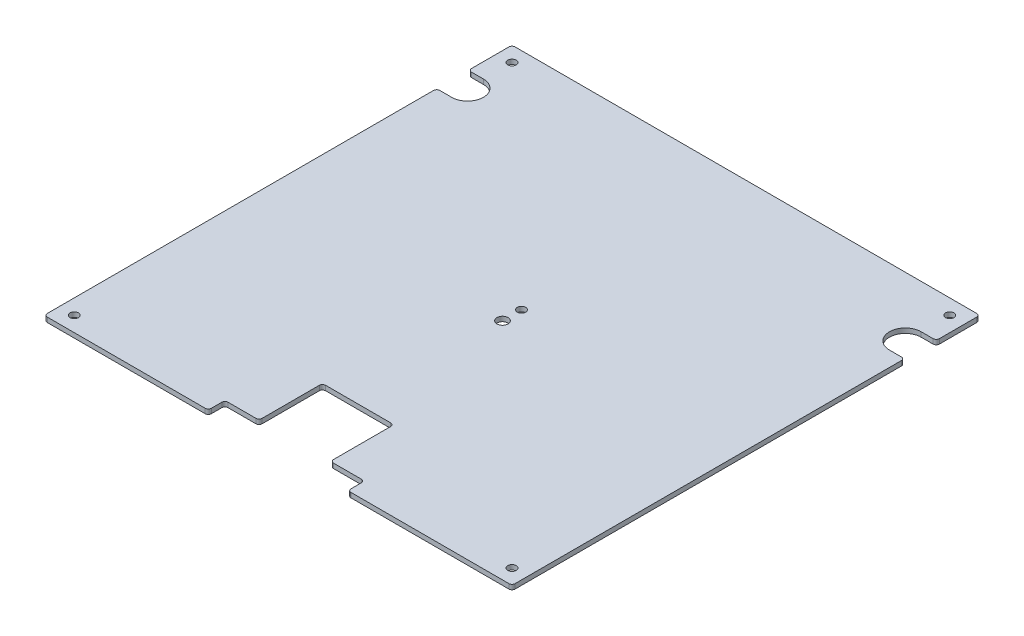
SolidWorks part; units mm, degrees
material "6061-T6 (SS)"
ref_plane "Front Plane" through (0, 0, 0) normal (0, 0, 1) x (1, 0, 0)
ref_plane "Top Plane" through (0, 0, 0) normal (0, 1, 0) x (1, 0, 0)
ref_plane "Right Plane" through (0, 0, 0) normal (1, 0, 0) x (0, 0, -1)
sketch "Sketch1" plane through (0, 0, 0) normal (0, 1, 0) x (1, 0, 0)
  line L1 (152, -152) -> (-152, -152)
  line L2 (152, -152) -> (152, 152)
  line L3 (152, 152) -> (-152, 152)
  line L4 (-152, -152) -> (-152, 152)
  line L5 (152, -152) -> (-152, 152) construction
  line L6 (152, 152) -> (-152, -152) construction
  point P0 (0, 0)
  dimension "D1" = 304
extrude "Boss-Extrude1" add sketch "Sketch1" along normal blind 3
sketch "Sketch2" plane through (0, 3, 0) normal (0, 1, 0) x (1, 0, 0)
  line L0 (-44, -152) -> (-44, -137)
  line L1 (-152, -152) -> (152, -152) construction
  line L2 (-44, -137) -> (44, -137)
  line L3 (44, -137) -> (44, -152)
  line L4 (44, -152) -> (-44, -152)
  line L5 (-152, 100) -> (-138, 100)
  line L6 (-152, 152) -> (-152, -152) construction
  line L8 (-138, 120) -> (-152, 120)
  line L9 (-152, 120) -> (-152, 100)
  line L10 (-152, 110) -> (-138, 110) construction
  line L11 (0, -152) -> (0, 152) construction
  line L12 (152, 152) -> (-152, 152) construction
  line L13 (152, 100) -> (138, 100)
  line L14 (152, 120) -> (152, 100)
  line L15 (138, 120) -> (152, 120)
  arc A0 (-138, 100) -> (-138, 120) centre (-138, 110) ccw
  arc A1 (138, 100) -> (138, 120) centre (138, 110) cw
  point P20 (0, 0)
  dimension "D1" = 108
  dimension "D2" = 196
  dimension "D3" = 15
  dimension "D4" = 20
  dimension "D5" = 262
  dimension "D6" = 14
extrude "Cut-Extrude1" cut sketch "Sketch2" against normal through all
sketch "Sketch7" plane through (0, 0, 0) normal (0, -1, 0) x (1, 0, 0)
  line L0 (44, 137) -> (-44, 137) construction
  line L1 (22.5, 97) -> (-22.5, 97)
  line L2 (22.5, 97) -> (22.5, 137)
  line L3 (22.5, 137) -> (-22.5, 137)
  line L4 (-22.5, 97) -> (-22.5, 137)
  line L5 (22.5, 97) -> (-22.5, 137) construction
  line L6 (22.5, 137) -> (-22.5, 97) construction
  point P0 (0, 117)
  dimension "D1" = 45
  dimension "D2" = 40
extrude "Cut-Extrude2" cut sketch "Sketch7" against normal up to surface (3 mm away) up to face at (0, 3, -18.875)
hole_wizard "Ø7.0 (7) Diameter Hole1" positions "Sketch3" profile "Sketch4" hole size "Ø7.0" standard "ANSI Metric" end condition up to next
sketch "Sketch3" plane through (0, 3, 0) normal (0, 1, 0) x (1, 0, 0)
  line L1 (-138, -138) -> (138, -138)
  line L2 (-138, -138) -> (-138, 138)
  line L3 (-138, 138) -> (138, 138)
  line L4 (138, -138) -> (138, 138)
  line L7 (0, 6) -> (0, -6) construction
  line L8 (-152, 100) -> (-152, -152) construction
  line L9 (-152, -152) -> (-44, -152) construction
  point P138 (0, -6)
  dimension "D1" = 14
  dimension "D2" = 152
  dimension "D3" = 290
  dimension "D4" = 14
  dimension "D5" = 146
  dimension "D6" = 158
  dimension "D7" = 290
sketch "Sketch4" plane through (0, 3, 6) normal (1, 0, 0) x (0, 0, 1)
  line L0 (0, 0) -> (0, 3)
  line L1 (0, 3) -> (3.5, 3)
  line L2 (3.5, 3) -> (3.5, 0)
  line L5 (3.5, 0) -> (0, 0)
  line L11 (0, -6.35) -> (0, 107.95) construction
  dimension "Thru Hole Dia." = 7
  dimension "Thru Hole Depth" = 3
hole_wizard "M5 Clearance Hole1" positions "Sketch5" profile "Sketch6" hole size "M5" standard "ANSI Metric" end condition up to next
sketch "Sketch5" plane through (0, 3, 0) normal (0, 1, 0) x (1, 0, 0)
  point P0 (-138, 138)
  point P3 (138, 138)
  point P6 (138, -138)
  point P9 (-138, -138)
  point P13 (0, 6)
sketch "Sketch6" plane through (-138, 3, -138) normal (1, 0, 0) x (0, 0, 1)
  line L0 (0, 0) -> (0, 3)
  line L1 (0, 3) -> (2.65, 3)
  line L2 (2.65, 3) -> (2.65, 0)
  line L5 (2.65, 0) -> (0, 0)
  line L11 (0, -6.35) -> (0, 107.95) construction
  dimension "Thru Hole Dia." = 5.3
  dimension "Thru Hole Depth" = 3
sketch "Sketch8" plane through (0, 3, 0) normal (0, 1, 0) x (1, 0, 0)
  line L1 (147.5, -147.5) -> (-147.5, -147.5)
  line L2 (147.5, -147.5) -> (147.5, 147.5)
  line L3 (147.5, 147.5) -> (-147.5, 147.5)
  line L4 (-147.5, -147.5) -> (-147.5, 147.5)
  line L5 (147.5, -147.5) -> (-147.5, 147.5) construction
  line L6 (147.5, 147.5) -> (-147.5, -147.5) construction
  point P0 (0, 0)
  dimension "D1" = 295
extrude "Cut-Extrude3" cut sketch "Sketch8" against normal through all flip side to cut
fillet "Fillet1" radius 2 16 edges at (-147.5, 1.5, -120) (-147.5, 1.5, -100) (-147.5, 1.5, 147.5) (-44, 1.5, 147.5) (-44, 1.5, 137) (-22.5, 1.5, 137) (-22.5, 1.5, 97) (22.5, 1.5, 97) (22.5, 1.5, 137) (44, 1.5, 137) (44, 1.5, 147.5) (147.5, 1.5, 147.5) (147.5, 1.5, -100) (147.5, 1.5, -120) (147.5, 1.5, -147.5) (-147.5, 1.5, -147.5)
